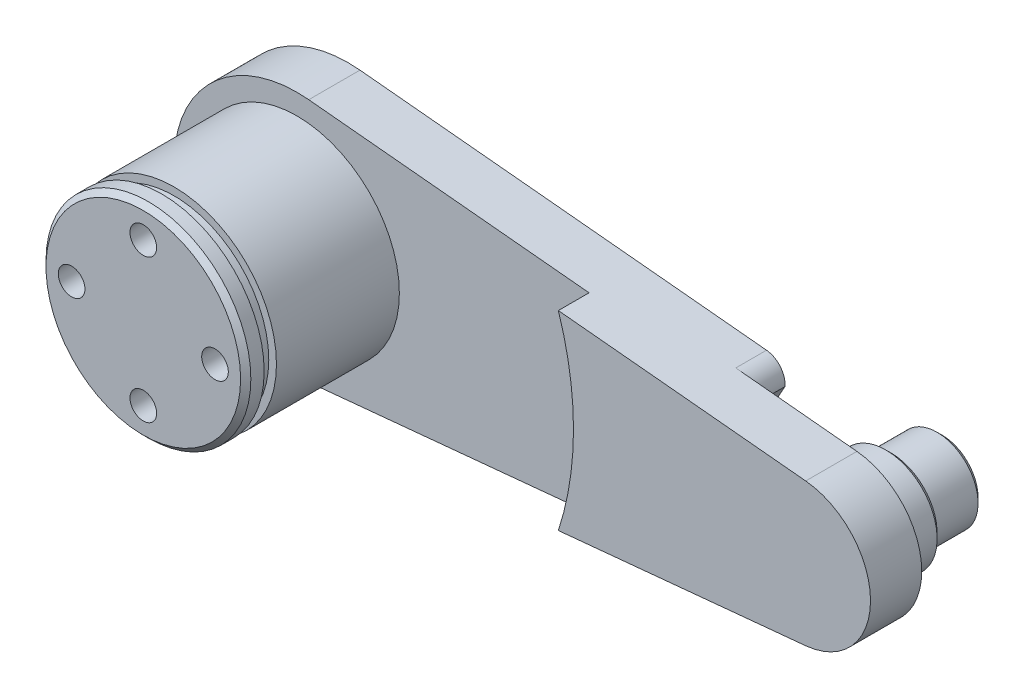
SolidWorks part; units mm, degrees
material "PEI"
ref_plane "前视基准面" through (0, 0, 0) normal (0, 0, 1) x (1, 0, 0)
ref_plane "上视基准面" through (0, 0, 0) normal (0, 1, 0) x (1, 0, 0)
ref_plane "右视基准面" through (0, 0, 0) normal (1, 0, 0) x (0, 0, -1)
other "Configuration Table"
sketch "草图1" plane through (0, 0, 0) normal (0, 0, 1) x (1, 0, 0)
  line L0 (0, 0) -> (52, 0) construction
  line L1 (1.1538, 11.9444) -> (52.6731, 6.9676)
  line L2 (1.1538, -11.9444) -> (52.6731, -6.9676)
  circle A0 centre (0, 0) radius 12
  circle A1 centre (52, 0) radius 7
  dimension "D2" = 24
  dimension "D3" = 14
  dimension "D1" = 52
extrude "凸台-拉伸1" add sketch "草图1" along normal blind 5 contours A0 L0 A1 | A0 | L0 A0 A1 | A1 region at (27.007, 5.0261, 0) region at (8.6326, -7.8389, 0) region at (27.007, -5.0261, 0) region at (47.4273, 5.0357, 0)
sketch "草图2" plane through (0, 0, 5) normal (0, 0, 1) x (1, 0, 0)
  arc A0 (1.1538, 11.9444) -> (1.1538, -11.9444) centre (0, 0) ccw construction
  arc A1 (1.1538, 11.9444) -> (1.1538, -11.9444) centre (0, 0) ccw
  circle A2 centre (0, 0) radius 12
  circle A3 centre (0, 0) radius 10
  dimension "D1" = 20
extrude "凸台-拉伸2" add sketch "草图2" along normal blind 15 contours A3 region at (0, 0, 5)
sketch "草图3" plane through (0, 0, 0) normal (0, 0, -1) x (-1, 0, 0)
  arc A0 (-52.6731, 6.9676) -> (-52.6731, -6.9676) centre (-52, 0) ccw construction
  arc A1 (-52.6731, 6.9676) -> (-52.6731, -6.9676) centre (-52, 0) ccw
  circle A2 centre (-52, 0) radius 4
  dimension "D1" = 8
extrude "凸台-拉伸3" add sketch "草图3" along normal blind 6 contours A2 region at (52, 0, 0)
sketch "草图4" plane through (0, 0, 0) normal (0, 0, -1) x (-1, 0, 0)
  circle A0 centre (-52, 0) radius 4 construction
  circle A1 centre (-52, 0) radius 4
  circle A2 centre (-52, 0) radius 5
  dimension "D1" = 1
extrude "凸台-拉伸4" add sketch "草图4" along normal blind 1
chamfer "倒角1" distance 0.5 angle 45 3 edges at (10, 0, 20) (47, 0, -1) (48, 0, -6)
sketch "草图6" plane through (0, 0, 20) normal (0, 0, 1) x (1, 0, 0)
  circle A0 centre (0, 0) radius 7 construction
  circle A1 centre (0, 7) radius 1.3
  circle A2 centre (7, 0) radius 1.3
  circle A3 centre (0, -7) radius 1.3
  circle A4 centre (-7, 0) radius 1.3
  point P14 (0, 0)
  dimension "D1" = 14
  dimension "D2" = 2.6
  dimension "D3" = 4
extrude "切除-拉伸2" cut sketch "草图6" against normal blind 6
sketch "草图11" plane through (0, 0, -6) normal (0, 0, -1) x (-1, 0, 0)
  circle A0 centre (-52, 0) radius 2.2
  dimension "D1" = 4.4
extrude "切除-拉伸7" cut sketch "草图11" against normal blind 10
sketch "草图12" plane through (0, 0, 5) normal (0, 0, 1) x (1, 0, 0)
  line L0 (0.9615, 9.9537) -> (52.4808, 4.9768)
  line L1 (0.9615, -9.9537) -> (52.4808, -4.9768)
  circle A0 centre (52, 0) radius 5 construction
  circle A1 centre (0, 0) radius 10 construction
  circle A2 centre (52, 0) radius 5
  circle A3 centre (0, 0) radius 10
  circle A4 centre (0, 0) radius 12
  circle A6 centre (52, 0) radius 7
  dimension "D1" = 2
extrude "切除-拉伸8" cut sketch "草图12" against normal blind 5 contours A6 L0 A4 L1 region at (26.8829, 0, 5)
sketch "草图14" plane through (0, 0, 0) normal (0, 0, -1) x (-1, 0, 0)
  circle A0 centre (-52, 0) radius 11.075
  circle A1 centre (-52, 0) radius 5 construction
  circle A2 centre (-52, 0) radius 5
  circle M2 centre (-52, 0) radius 5
  line M3 (-52.6731, -6.9676) -> (-1.1538, -11.9444)
  line M5 (-1.1538, 11.9444) -> (-52.6731, 6.9676)
  arc M6 (-52.6731, 6.9676) -> (-52.6731, -6.9676) centre (-52, 0) ccw
  dimension "D1" = 22.15
extrude "切除-拉伸9" cut sketch "草图14" against normal blind 3 contours A0 M5 M3 M6 | A0 M3 M5 M6 M2 region at (41.9784, -4.1224, 0) region at (48.4298, 7.6703, 0)
sketch "草图15" plane through (0, 0, 5) normal (0, 0, 1) x (1, 0, 0)
  line L6 (1.1538, -11.9444) -> (52.6731, -6.9676)
  line L7 (52.6731, 6.9676) -> (1.1538, 11.9444)
  line L8 (1.1538, -11.9444) -> (52.6731, -6.9676)
  line L9 (52.6731, 6.9676) -> (1.1538, 11.9444)
  arc A6 (52.6731, -6.9676) -> (52.6731, 6.9676) centre (52, 0) ccw
  arc A7 (1.1538, 11.9444) -> (1.1538, -11.9444) centre (0, 0) ccw
  arc A8 (52.6731, -6.9676) -> (52.6731, 6.9676) centre (52, 0) ccw
  arc A9 (1.1538, 11.9444) -> (1.1538, -11.9444) centre (0, 0) ccw
  circle M1 centre (0, 0) radius 10
  line M2 (1.1538, -11.9444) -> (52.6731, -6.9676)
  arc M3 (52.6731, -6.9676) -> (52.6731, 6.9676) centre (52, 0) ccw
  line M4 (52.6731, 6.9676) -> (1.1538, 11.9444)
  arc M5 (1.1538, 11.9444) -> (1.1538, -11.9444) centre (0, 0) ccw
  line M6 (7.5641, 9.3159) -> (47.6045, 5.4479)
  arc M7 (47.6045, 5.4479) -> (47.6045, -5.4479) centre (52, 0) ccw
  line M8 (47.6045, -5.4479) -> (7.5641, -9.3159)
  arc M9 (7.5641, -9.3159) -> (7.5641, 9.3159) centre (0, 0) ccw
  dimension "D1" = 0
extrude "凸台-拉伸5" add sketch "草图15" against normal blind 1 contours M6 M8 M7 | M5 M2 M3 M4 M9 M6 M7 M8 M1 region at (-11.2505, 0, 5) region at (26.8829, 0, 5)
fillet "圆角1" radius 2 2 edges at (44.1306, -7.7928, 1.5) (44.1306, 7.7928, 1.5)
sketch "草图16" plane through (0, 0, 0) normal (0, 1, 0) x (1, 0, 0)
  line L0 (-9.5, -20) -> (9.5, -20) construction
  line L1 (9.25, -17) -> (13.9131, -17)
  line L2 (9.25, -17) -> (9.25, -18.2)
  line L3 (9.25, -18.2) -> (13.9131, -18.2)
  line L4 (13.9131, -17) -> (13.9131, -18.2)
  line L5 (0, -20) -> (0, 0) construction
  dimension "D1" = 1.2
  dimension "D2" = 3
  dimension "D3" = 9.25
revolve "切除-旋转1" cut sketch "草图16" angle 360 about L5
sketch "草图17" plane through (0, 0, 4) normal (0, 0, -1) x (-1, 0, 0)
  line L2 (-7.5641, 9.3159) -> (-47.6045, 5.4479)
  line L3 (-47.6045, -5.4479) -> (-7.5641, -9.3159)
  line L4 (-7.5641, 9.3159) -> (-42.6445, 5.927)
  line L5 (-42.6445, -5.927) -> (-7.5641, -9.3159)
  line L9 (-38.6445, 2.2948) -> (-38.6445, -2.2948)
  line L10 (-38.6445, -2.2948) -> (-15.3406, -4.546)
  line L11 (-15.3406, 4.546) -> (-38.6445, 2.2948)
  line L14 (-42.6445, 5.927) -> (-42.6445, -5.927) construction
  arc A2 (-7.5641, 9.3159) -> (-7.5641, -9.3159) centre (0, 0) ccw
  arc A3 (-47.6045, -5.4479) -> (-47.6045, 5.4479) centre (-52, 0) ccw
  arc A4 (-7.5641, 9.3159) -> (-7.5641, -9.3159) centre (0, 0) ccw
  arc A10 (-15.3406, 4.546) -> (-15.3406, -4.546) centre (0, 0) ccw
  arc A11 (-42.6445, -5.927) -> (-42.6445, 5.927) centre (-52, 0) ccw
  dimension "D1" = 0
extrude "凸台-拉伸6" add sketch "草图17" along normal up to surface (4 mm away) up to face at (22.0754, 0, 0)
sketch "草图18" plane through (0, 0, 4) normal (0, 0, -1) x (-1, 0, 0)
  line L4 (-42.6445, 5.927) -> (-47.6045, 5.4479)
  line L5 (-47.6045, -5.4479) -> (-42.6445, -5.927)
  line L7 (-42.6445, 5.927) -> (-47.6045, 5.4479)
  line L8 (-47.6045, -5.4479) -> (-42.6445, -5.927)
  arc A1 (-47.6045, -5.4479) -> (-47.6045, 5.4479) centre (-52, 0) ccw
  arc A2 (-47.6045, -5.4479) -> (-47.6045, 5.4479) centre (-52, 0) ccw
  arc A4 (-42.6445, -5.927) -> (-42.6445, 5.927) centre (-52, 0) ccw
  arc A5 (-42.6445, -5.927) -> (-42.6445, 5.927) centre (-52, 0) ccw
  dimension "D1" = 0
extrude "凸台-拉伸7" add sketch "草图18" along normal up to surface (1 mm away) up to face at (47, 0, 3)
sketch "草图19" plane through (0, 0, 5) normal (0, 0, 1) x (1, 0, 0)
  line L2 (1.1538, -11.9444) -> (52.6731, -6.9676)
  line L3 (52.6731, 6.9676) -> (1.1538, 11.9444)
  line L4 (28.5219, -9.3006) -> (52.6731, -6.9676)
  line L5 (52.6731, 6.9676) -> (28.5219, 9.3006)
  arc A0 (28.5219, -9.3006) -> (28.5219, 9.3006) centre (0, 0) ccw
  arc A2 (52.6731, -6.9676) -> (52.6731, 6.9676) centre (52, 0) ccw
  arc A3 (1.1538, 11.9444) -> (1.1538, -11.9444) centre (0, 0) ccw
  arc A4 (52.6731, -6.9676) -> (52.6731, 6.9676) centre (52, 0) ccw
  dimension "D2" = 60
  dimension "D1" = 0
extrude "凸台-拉伸8" add sketch "草图19" along normal blind 3
equation "\"D1@草图1\"= \"主动杆_后_长度\""
equation "\"主动杆_后_长度\"= 52"
